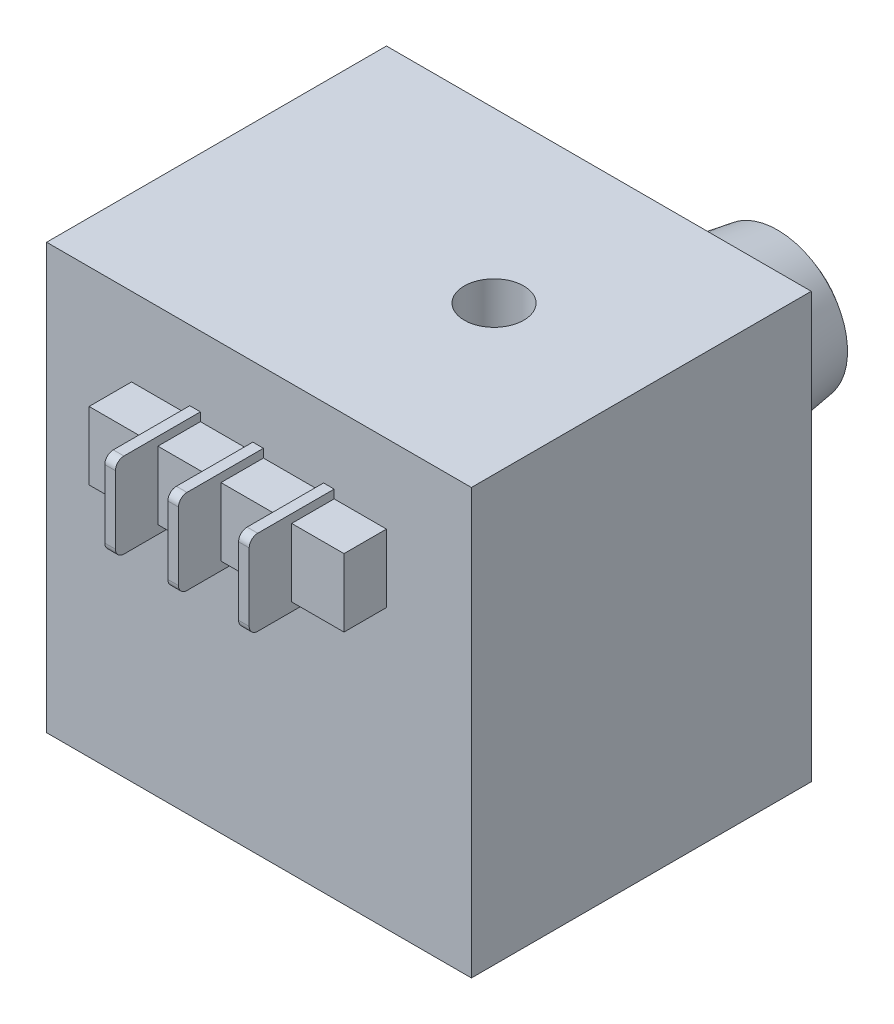
SolidWorks part; units mm, degrees
material "6061 Alloy"
ref_plane "Front Plane" through (0, 0, 0) normal (0, 0, 1) x (1, 0, 0)
ref_plane "Top Plane" through (0, 0, 0) normal (0, 1, 0) x (1, 0, 0)
ref_plane "Right Plane" through (0, 0, 0) normal (1, 0, 0) x (0, 0, -1)
sketch "Sketch1" plane through (0, 0, 0) normal (0, 0, 1) x (1, 0, 0)
  line L1 (-31.75, 31.75) -> (31.75, 31.75)
  line L2 (-31.75, 31.75) -> (-31.75, -31.75)
  line L3 (-31.75, -31.75) -> (31.75, -31.75)
  line L4 (31.75, 31.75) -> (31.75, -31.75)
  line L5 (-31.75, 31.75) -> (31.75, -31.75) construction
  line L6 (-31.75, -31.75) -> (31.75, 31.75) construction
  point P0 (0, 0)
  dimension "D1" = 63.5
  dimension "D2" = 63.5
extrude "Boss-Extrude1" add sketch "Sketch1" along normal blind 50.8
sketch "Sketch2" plane through (0, 0, 0) normal (0, 0, -1) x (-1, 0, 0)
  circle A0 centre (0, 0) radius 2.54
  dimension "D1" = 5.08
extrude "Boss-Extrude2" add sketch "Sketch2" along normal blind 12.7
sketch "Sketch3" plane through (0, 0, -12.7) normal (0, 0, -1) x (-1, 0, 0)
  circle A0 centre (0, 0) radius 12.7
  dimension "D1" = 25.4
extrude "Boss-Extrude3" add sketch "Sketch3" along normal blind 15.24 draft 9 and the other way blind 10.16 draft 9 other way draft outward yes
sketch "Sketch4" plane through (0, 0, -27.94) normal (0, 0, -1) x (-1, 0, 0)
  circle A0 centre (0, 0) radius 18.5363
extrude "Boss-Extrude4" add sketch "Sketch4" along normal blind 3.175 draft 58 from offset 25.4 offset against normal yes
chamfer "Chamfer1" distance 1.27 angle 45 1 edges at (-10.2862, 0, -27.94) first distance on face at (-10.2862, 0, -27.94)
sketch "Sketch6" plane through (0, 0, 50.8) normal (0, 0, 1) x (1, 0, 0)
  line L1 (-19.05, 9.8537) -> (19.05, 9.8537)
  line L2 (-19.05, 9.8537) -> (-19.05, 20.0137)
  line L3 (-19.05, 20.0137) -> (19.05, 20.0137)
  line L4 (19.05, 9.8537) -> (19.05, 20.0137)
  line L5 (-19.05, 9.8537) -> (19.05, 20.0137) construction
  line L6 (-19.05, 20.0137) -> (19.05, 9.8537) construction
  point P0 (0, 14.9337)
  dimension "D1" = 38.1
  dimension "D2" = 10.16
extrude "Boss-Extrude6" add sketch "Sketch6" along normal blind 6.35
sketch "Sketch7" plane through (0, 0, 57.15) normal (0, 0, 1) x (1, 0, 0)
  line L0 (-10.351, 8.5837) -> (-8.7635, 8.5837)
  line L1 (-0.925, 8.5837) -> (0.6625, 8.5837)
  line L2 (-0.925, 8.5837) -> (-0.925, 21.2837)
  line L3 (-0.925, 21.2837) -> (0.6625, 21.2837)
  line L4 (0.6625, 8.5837) -> (0.6625, 21.2837)
  line L5 (-0.925, 8.5837) -> (0.6625, 21.2837) construction
  line L6 (-0.925, 21.2837) -> (0.6625, 8.5837) construction
  line L7 (-10.351, 8.5837) -> (-10.351, 21.2837)
  line L8 (-10.351, 21.2837) -> (-8.7635, 21.2837)
  line L9 (-8.7635, 8.5837) -> (-8.7635, 21.2837)
  line L10 (9.6463, 8.5837) -> (11.2338, 8.5837)
  line L11 (9.6463, 8.5837) -> (9.6463, 21.2837)
  line L12 (9.6463, 21.2837) -> (11.2338, 21.2837)
  line L13 (11.2338, 8.5837) -> (11.2338, 21.2837)
  line L14 (-19.05, 20.0137) -> (-19.05, 9.8537) construction
  point P0 (-0.1312, 14.9337)
  point P15 (-19.05, 14.9337)
  point P16 (-10.351, 14.9337)
  point P17 (-0.925, 14.9337)
  point P18 (9.6463, 14.9337)
  dimension "D1" = 12.7
  dimension "D2" = 1.5875
extrude "Boss-Extrude7" add sketch "Sketch7" along normal blind 6.35 and the other way blind 6.35
fillet "Fillet1" radius 1.27 6 edges at (10.44, 21.2837, 63.5) (10.44, 8.5837, 63.5) (-0.1312, 21.2837, 63.5) (-0.1312, 8.5837, 63.5) (-9.5573, 8.5837, 63.5) (-9.5573, 21.2837, 63.5)
sketch "Sketch8" plane through (0, 31.75, 0) normal (0, 1, 0) x (1, 0, 0)
  circle A0 centre (9.5703, -25.24) radius 4.445
  dimension "D1" = 8.89
extrude "Cut-Extrude1" cut sketch "Sketch8" against normal blind 7.62
